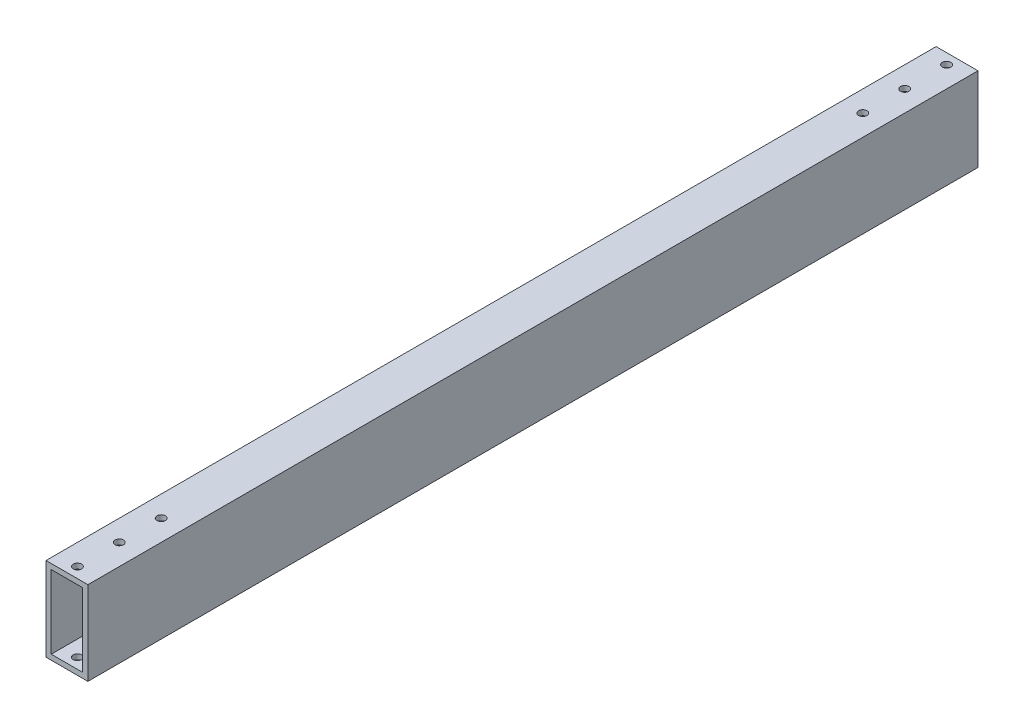
SolidWorks part; units mm, degrees
material "6061-T6 (SS)"
ref_plane "Front" through (0, 0, 0) normal (0, 0, 1) x (1, 0, 0)
ref_plane "Top" through (0, 0, 0) normal (0, 1, 0) x (1, 0, 0)
ref_plane "Right" through (0, 0, 0) normal (1, 0, 0) x (0, 0, -1)
sketch "Sketch1" plane through (0, 0, 0) normal (0, 0, 1) x (1, 0, 0)
  line L1 (-12.7, -25.4) -> (12.7, -25.4)
  line L2 (-12.7, -25.4) -> (-12.7, 25.4)
  line L3 (-12.7, 25.4) -> (12.7, 25.4)
  line L4 (12.7, -25.4) -> (12.7, 25.4)
  line L5 (-12.7, -25.4) -> (12.7, 25.4) construction
  line L6 (-12.7, 25.4) -> (12.7, -25.4) construction
  point P0 (0, 0)
  dimension "D1" = 25.4
  dimension "D2" = 50.8
extrude "Extrude-Thin1" add sketch "Sketch1" along normal blind 539.75 thin thin type one direction reverse wall 3.175
hole_wizard "#10 Clearance Hole1" positions "Sketch2" profile "Sketch3" hole size "#10" standard "ANSI Inch" end condition through all
sketch "Sketch2" plane through (0, 25.4, 0) normal (0, 1, 0) x (1, 0, 0)
  line L0 (-12.7, -539.75) -> (-12.7, 0) construction
  line L1 (12.7, -539.75) -> (-12.7, -539.75) construction
  point P0 (0, -533.4)
  point P2 (0, -508)
  point P4 (0, -482.6)
  point P6 (0, -6.35)
  point P8 (0, -31.75)
  point P10 (0, -57.15)
  dimension "D1" = 12.7
  dimension "D2" = 25.4
  dimension "D3" = 6.35
  dimension "D4" = 25.4
  dimension "D5" = 6.35
  dimension "D6" = 25.4
  dimension "D7" = 25.4
sketch "Sketch3" plane through (0, 25.4, 533.4) normal (1, 0, 0) x (0, 0, 1)
  line L0 (0, 0) -> (0, 50.8)
  line L1 (0, 50.8) -> (2.5527, 50.8)
  line L2 (2.5527, 50.8) -> (2.5527, 0)
  line L5 (2.5527, 0) -> (0, 0)
  line L11 (0, -6.35) -> (0, 107.95) construction
  dimension "Thru Hole Dia." = 5.1054
  dimension "Thru Hole Depth" = 50.8
